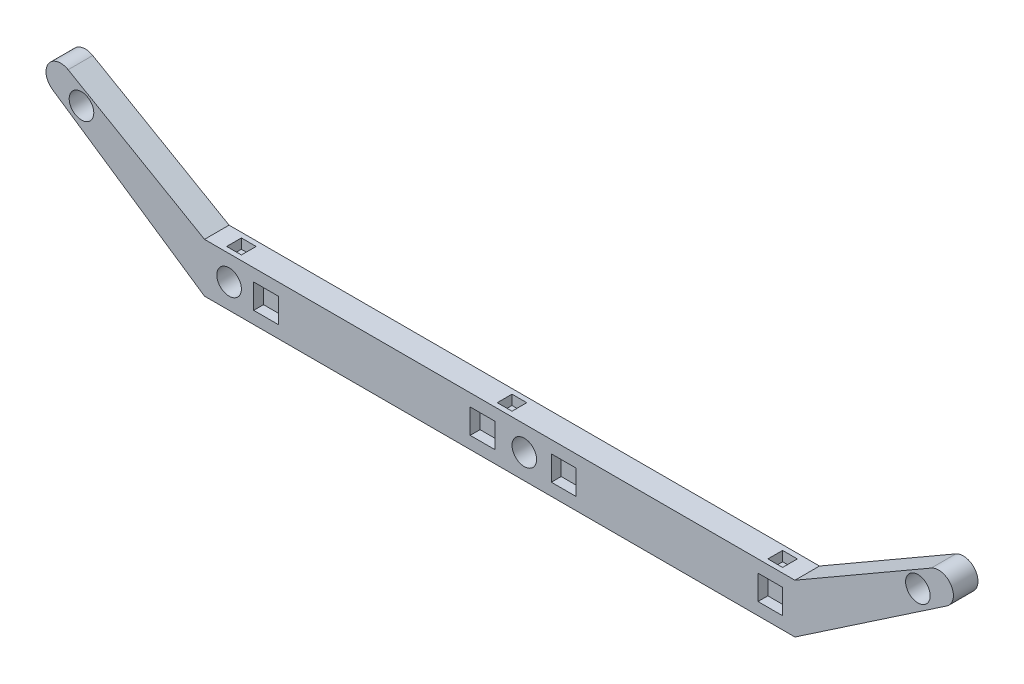
SolidWorks part; units mm, degrees
ref_plane "Front Plane" through (0, 0, 0) normal (0, 0, 1) x (1, 0, 0)
ref_plane "Top Plane" through (0, 0, 0) normal (0, 1, 0) x (1, 0, 0)
ref_plane "Right Plane" through (0, 0, 0) normal (1, 0, 0) x (0, 0, -1)
sketch "Sketch1" plane through (0, 0, 0) normal (1, 0, 0) x (0, 0, -1)
  line L1 (-25, 50) -> (25, 50)
  line L2 (-25, 50) -> (-25, -50)
  line L3 (-25, -50) -> (25, -50)
  line L4 (25, 50) -> (25, -50)
  line L5 (-25, 50) -> (25, -50) construction
  line L6 (-25, -50) -> (25, 50) construction
  point P0 (0, 0)
  dimension "D1" = 50
  dimension "D2" = 100
extrude "Boss-Extrude1" add sketch "Sketch1" along normal blind 600 and the other way blind 600
sketch "Sketch2" plane through (0, 0, 25) normal (0, 0, 1) x (1, 0, 0)
  line L0 (600, 50) -> (877.1281, 210)
  line L1 (908.9475, 159.1776) -> (600, -50)
  line L2 (600, 50) -> (1167.3473, 50) construction
  line L3 (600, 50) -> (600, -50)
  line L4 (0, -50) -> (0, 50) construction
  line L5 (-600, -50) -> (600, -50) construction
  line L6 (-600, 50) -> (600, 50) construction
  line L7 (-600, 50) -> (-600, -50)
  line L8 (-908.9475, 159.1776) -> (-600, -50)
  line L9 (-600, 50) -> (-877.1281, 210)
  arc A0 (877.1281, 210) -> (908.9475, 159.1776) centre (892.1281, 184.0192) cw
  arc A1 (-877.1281, 210) -> (-908.9475, 159.1776) centre (-892.1281, 184.0192) ccw
  dimension "D2" = 30
  dimension "D1" = 30
  dimension "D3" = 320
extrude "Boss-Extrude2" add sketch "Sketch2" against normal blind 50
sketch "Sketch3" plane through (0, 0, 25) normal (0, 0, 1) x (1, 0, 0)
  line L0 (0, 0) -> (0, 50) construction
  line L1 (-600, 50) -> (600, 50) construction
  circle A0 centre (-850, 160) radius 25
  circle A1 centre (850, 160) radius 25
  point P0 (-850, 160)
extrude "Cut-Extrude1" cut sketch "Sketch3" against normal blind 50
sketch "Sketch4" plane through (0, 0, 25) normal (0, 0, 1) x (1, 0, 0)
  line L0 (0, 0) -> (50, 0) construction
  line L1 (-600, -50) -> (-600, 50) construction
  line L2 (-600, 0) -> (-550, 0) construction
  circle A0 centre (50, 0) radius 25
  circle A1 centre (-550, 0) radius 25
  dimension "D2" = 50
  dimension "D1" = 50
extrude "Cut-Extrude2" cut sketch "Sketch4" against normal through all
sketch "Sketch5" plane through (0, 0, 25) normal (0, 0, 1) x (1, 0, 0)
  line L0 (0, 0) -> (-10, 0) construction
  line L1 (0, 0) -> (0, 50) construction
  line L2 (-600, 50) -> (600, 50) construction
  line L3 (0, 0) -> (-10, 0) construction
  line L8 (-475, 0) -> (0, 0) construction
  line L9 (-60, 25) -> (-10, 25)
  line L10 (-60, 25) -> (-60, -25)
  line L15 (-60, -25) -> (-10, -25)
  line L16 (-10, 25) -> (-10, -25)
  line L17 (-60, 25) -> (-10, -25) construction
  line L18 (-60, -25) -> (-10, 25) construction
  line L19 (-500, 25) -> (-450, 25)
  line L20 (-500, 25) -> (-500, -25)
  line L21 (-500, -25) -> (-450, -25)
  line L22 (-450, 25) -> (-450, -25)
  line L23 (-500, 25) -> (-450, -25) construction
  line L24 (-500, -25) -> (-450, 25) construction
  line L25 (105, 25) -> (105, -25)
  line L26 (155, -25) -> (105, -25)
  line L27 (155, 25) -> (155, -25)
  line L28 (155, 25) -> (105, 25)
  line L29 (525, 25) -> (525, -25)
  line L30 (575, -25) -> (525, -25)
  line L31 (575, 25) -> (575, -25)
  line L32 (575, 25) -> (525, 25)
  line L33 (50, 0) -> (-35, 0) construction
  point P1 (-475, 0)
  dimension "D1" = 50
  dimension "D2" = 50
  dimension "D3" = 50
  dimension "D4" = 50
  dimension "D5" = 475
  dimension "D6" = 85
extrude "Cut-Extrude3" cut sketch "Sketch5" against normal blind 20
sketch "Sketch6" plane through (0, 50, 0) normal (0, 1, 0) x (1, 0, 0)
  line L0 (-600, 25) -> (-550, 25) construction
  line L1 (-600, 25) -> (600, 25) construction
  line L2 (-550, 25) -> (-550, -25) construction
  line L3 (-600, -25) -> (600, -25) construction
  line L4 (0, -25) -> (0, 25) construction
  line L5 (565, -15) -> (535, -15)
  line L6 (-565, 15) -> (-535, 15)
  line L7 (-565, 15) -> (-565, -15)
  line L8 (-565, -15) -> (-535, -15)
  line L9 (-535, 15) -> (-535, -15)
  line L10 (-565, 15) -> (-535, -15) construction
  line L11 (-565, -15) -> (-535, 15) construction
  line L12 (-15, 15) -> (15, 15)
  line L13 (-15, 15) -> (-15, -15)
  line L14 (-15, -15) -> (15, -15)
  line L15 (15, 15) -> (15, -15)
  line L16 (-15, 15) -> (15, -15) construction
  line L17 (-15, -15) -> (15, 15) construction
  line L18 (565, 15) -> (535, 15)
  line L19 (565, 15) -> (565, -15)
  line L20 (535, 15) -> (535, -15)
  point P10 (-550, 0)
  point P15 (0, 0)
  dimension "D1" = 50
  dimension "D2" = 30
  dimension "D3" = 30
  dimension "D4" = 30
  dimension "D5" = 30
extrude "Cut-Extrude4" cut sketch "Sketch6" against normal blind 20
